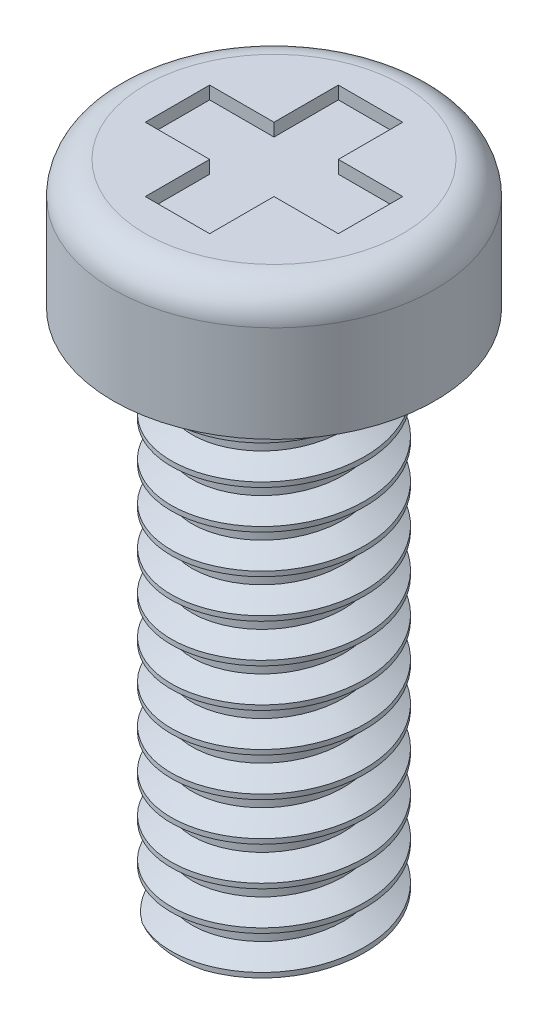
SolidWorks part; units mm, degrees
ref_plane "Front Plane" through (0, 0, 0) normal (0, 0, 1) x (1, 0, 0)
ref_plane "Top Plane" through (0, 0, 0) normal (0, 1, 0) x (1, 0, 0)
ref_plane "Right Plane" through (0, 0, 0) normal (1, 0, 0) x (0, 0, -1)
sketch "Sketch1" plane through (0, 0, 0) normal (0, 1, 0) x (1, 0, 0)
  circle A0 centre (-8.5774, -1.2719) radius 2.5
  dimension "D1" = 5
extrude "Boss-Extrude1" add sketch "Sketch1" along normal blind 2
sketch "Sketch2" plane through (0, 0, 0) normal (0, -1, 0) x (1, 0, 0)
  circle A0 centre (-8.5774, 1.2719) radius 1.5
  circle A1 centre (-8.5774, 1.2719) radius 2.5 construction
  dimension "D1" = 3
extrude "Boss-Extrude2" add sketch "Sketch2" along normal blind 8 contours A0
fillet "Fillet1" radius 0.5 1 edges at (-8.5774, 2, 3.7719)
sketch "Sketch4" plane through (0, 2, 0) normal (0, 1, 0) x (1, 0, 0)
  line L1 (-9.0774, 0.2281) -> (-8.0774, 0.2281)
  line L2 (-9.0774, 0.2281) -> (-9.0774, -2.7719)
  line L3 (-9.0774, -2.7719) -> (-8.0774, -2.7719)
  line L4 (-8.0774, 0.2281) -> (-8.0774, -2.7719)
  line L5 (-7.0774, -0.7719) -> (-10.0774, -0.7719)
  line L6 (-7.0774, -0.7719) -> (-7.0774, -1.7719)
  line L7 (-7.0774, -1.7719) -> (-10.0774, -1.7719)
  line L8 (-10.0774, -0.7719) -> (-10.0774, -1.7719)
  circle A0 centre (-8.5774, -1.2719) radius 0.1608
  circle A1 centre (-8.5774, -1.2719) radius 2 construction
  point P12 (-8.5774, -0.7719)
  point P13 (-8.0774, -1.2719)
  point P14 (0, 0)
  point P15 (-7.0774, -1.2719)
  point P16 (-8.5774, 0.2281)
  dimension "D1" = 1
  dimension "D2" = 1
  dimension "D3" = 3
  dimension "D4" = 3
extrude "Cut-Extrude1" cut sketch "Sketch4" against normal blind 0.2 contours L5 L4 L1 L2 | L7 L4 L5 L2 A0 | L5 L8 L7 L2 | L4 L7 L2 L3 | L7 L6 L5 L4 | A0 region at (-8.5774, 2, 0.2719) region at (-8.5774, 2, 0.7861) region at (-9.5774, 2, 1.2719) region at (-7.5774, 2, 1.2719) region at (-8.5774, 2, 2.2719) region at (-8.5774, 2, 1.2719)
thread "Thread1" pitch 0.6 method cut profile "Thread Profile1" start angle 0, offset 1, length 0, pitch 0.6, diameter 3
ref_plane "Plane1" through (-7.0774, -9, 1.2719) normal (0, 0, 1) x (1, 0, 0)
sketch "Thread Profile1" plane through (-7.0774, -9, 1.2719) normal (0, 0, 1) x (1, 0, 0)
  line L0 (0, 0) -> (0, 0.6) construction
  line L11 (0, 0) -> (0, 0.525)
  line L12 (0, 0.525) -> (-0.3248, 0.3375)
  line L13 (-0.3248, 0.3375) -> (-0.3248, 0.1875)
  line L15 (-0.3248, 0.1875) -> (0, 0)
  line L17 (-0.3248, 0.2625) -> (0, 0.2625) construction
  point P2 (0, 0)
  dimension "Pitch" = 0.6
  dimension "Profile_Angle" = 60
  dimension "Profile_Land" = 0.15
  dimension "Profile_Height" = 0.3248
